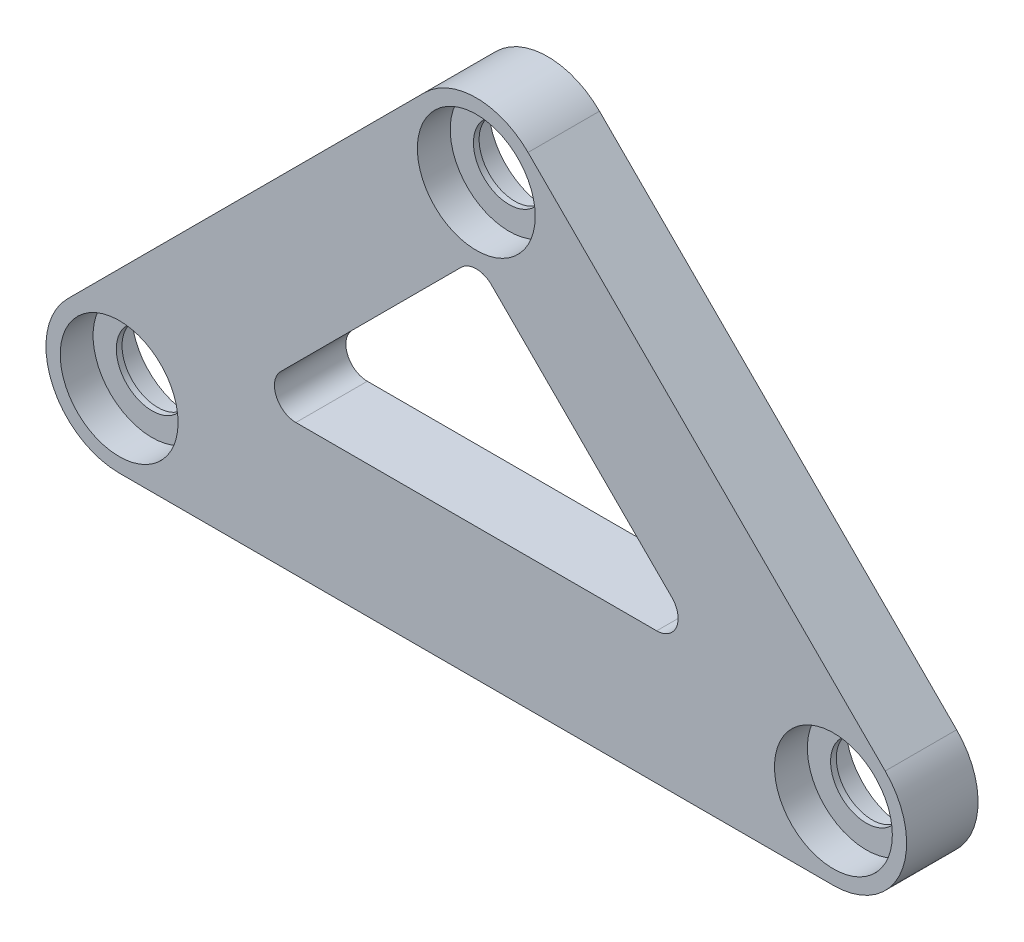
SolidWorks part; units mm, degrees
ref_plane "Front Plane" through (0, 0, 0) normal (0, 0, 1) x (1, 0, 0)
ref_plane "Top Plane" through (0, 0, 0) normal (0, 1, 0) x (1, 0, 0)
ref_plane "Right Plane" through (0, 0, 0) normal (1, 0, 0) x (0, 0, -1)
sketch "Sketch2" plane through (0, 0, 0) normal (0, 0, 1) x (1, 0, 0)
  line L0 (-100, 0) -> (0, 0) construction
  line L1 (-100, 10.25) -> (0, 10.25)
  line L2 (-100, -10.25) -> (0, -10.25)
  line L3 (0, 0) -> (-50, 50) construction
  line L4 (-7.2478, -7.2478) -> (-57.2478, 42.7522)
  line L5 (7.2478, 7.2478) -> (-42.7522, 57.2478)
  line L6 (-100, 0) -> (-50, 50) construction
  line L7 (-107.2478, 7.2478) -> (-57.2478, 57.2478)
  line L8 (-92.7522, -7.2478) -> (-42.7522, 42.7522)
  arc A0 (-100, 10.25) -> (-100, -10.25) centre (-100, 0) ccw
  arc A1 (0, -10.25) -> (0, 10.25) centre (0, 0) ccw
  arc A2 (-7.2478, -7.2478) -> (7.2478, 7.2478) centre (0, 0) ccw
  arc A3 (-42.7522, 57.2478) -> (-57.2478, 42.7522) centre (-50, 50) ccw
  arc A4 (-107.2478, 7.2478) -> (-92.7522, -7.2478) centre (-100, 0) ccw
  arc A5 (-42.7522, 42.7522) -> (-57.2478, 57.2478) centre (-50, 50) ccw
  point P3 (-50, 0)
  point P8 (-25, 25)
  point P15 (-75, 25)
  point P22 (-19.863, 86.6025)
  point P23 (-22.8801, 46.2137)
  point P24 (-75.429, 10.25)
  point P25 (0, 0)
  dimension "D1" = 100
  dimension "D2" = 20.5
  dimension "D3" = 45
  dimension "D4" = 45
extrude "Boss-Extrude4" add sketch "Sketch2" along normal blind 10 contours A4 L2 A2 L4 L1 L8 | A0 A4 L8 L1 | A3 L7 A0 L1 L8 L4 | L8 A5 A3 L4 | A5 L8 L4 L1 A1 L5 | L4 A2 A1 L1 region at (-74.0722, 27.272, 0) region at (-96.1173, 1.6083, 0) region at (-50, -1.0132, 0) region at (-25.9278, 27.272, 0) region at (-3.8827, 1.6083, 0) region at (-50, 49.2802, 0)
sketch "Sketch3" plane through (0, 0, 0) normal (0, 0, -1) x (-1, 0, 0)
  line L0 (57.2478, 57.2478) -> (107.2478, 7.2478)
  line L1 (57.2478, 57.2478) -> (107.2478, 7.2478)
  line L2 (100, -10.25) -> (0, -10.25)
  line L3 (100, -10.25) -> (0, -10.25)
  line L4 (-7.2478, 7.2478) -> (42.7522, 57.2478)
  line L5 (-7.2478, 7.2478) -> (42.7522, 57.2478)
  circle A0 centre (0, 0) radius 8.25
  circle A1 centre (50, 50) radius 8.25
  circle A2 centre (100, 0) radius 8.25
  arc A3 (100, -10.25) -> (107.2478, 7.2478) centre (100, 0) ccw
  arc A4 (100, -10.25) -> (107.2478, 7.2478) centre (100, 0) ccw
  arc A5 (-7.2478, 7.2478) -> (0, -10.25) centre (0, 0) ccw
  arc A6 (-7.2478, 7.2478) -> (0, -10.25) centre (0, 0) ccw
  arc A7 (57.2478, 57.2478) -> (42.7522, 57.2478) centre (50, 50) ccw
  arc A8 (57.2478, 57.2478) -> (42.7522, 57.2478) centre (50, 50) ccw
  point P7 (0, 0)
  dimension "D1" = 16.5
  dimension "D2" = 16.5
  dimension "D3" = 16.5
extrude "Cut-Extrude1" cut sketch "Sketch3" against normal blind 4.6 contours A0 | A1 | A2 region at (0, 0, 0) region at (-50, 50, 0) region at (-100, 0, 0)
sketch "Sketch4" plane through (0, 0, 10) normal (0, 0, 1) x (1, 0, 0)
  circle A0 centre (-100, 0) radius 8.25
  circle A1 centre (-50, 50) radius 8.25
  circle A2 centre (0, 0) radius 8.25
  arc A3 (-107.2478, 7.2478) -> (-100, -10.25) centre (-100, 0) ccw construction
  arc A4 (-42.7522, 57.2478) -> (-57.2478, 57.2478) centre (-50, 50) ccw construction
  arc A5 (0, -10.25) -> (7.2478, 7.2478) centre (0, 0) ccw construction
  dimension "D1" = 16.5
  dimension "D2" = 16.5
  dimension "D3" = 16.5
extrude "Cut-Extrude2" cut sketch "Sketch4" against normal blind 4.6
sketch "Sketch5" plane through (0, 0, 0) normal (0, 0, -1) x (-1, 0, 0)
  line L2 (17.5, 8.25) -> (50, 40.75)
  line L3 (50, 40.75) -> (82.5, 8.25)
  line L4 (82.5, 8.25) -> (17.5, 8.25)
  circle A0 centre (0, 0) radius 8.25 construction
  circle A2 centre (50, 50) radius 8.25 construction
  point P5 (49.7507, 40.2057)
  point P6 (16.5082, 8.25)
  point P7 (0, 0)
  dimension "D3" = 45
  dimension "D1" = 9.25
  dimension "D2" = 45
extrude "Cut-Extrude3" cut sketch "Sketch5" against normal blind 16.6
sketch "Sketch6" plane through (0, 0, 10) normal (0, 0, 1) x (1, 0, 0)
  circle A1 centre (-100, 0) radius 5
  circle A2 centre (-50, 50) radius 5
  circle A3 centre (0, 0) radius 5
  circle A4 centre (-100, 0) radius 8.25 construction
  circle A6 centre (-50, 50) radius 8.25 construction
  circle A7 centre (0, 0) radius 8.25 construction
  dimension "D1" = 10
  dimension "D2" = 10
  dimension "D3" = 10
extrude "Cut-Extrude4" cut sketch "Sketch6" against normal blind 16.6
fillet "Fillet1" radius 3 3 edges at (-82.5, 8.25, 5) (-17.5, 8.25, 5) (-50, 40.75, 5)
equation "\"D4@Sketch2\"=\"D3@Sketch2\""
equation "\"D2@Sketch3\"=\"D1@Sketch3\""
equation "\"D3@Sketch3\"=\"D1@Sketch3\""
equation "\"D2@Sketch4\"=\"D1@Sketch4\""
equation "\"D3@Sketch4\"=\"D1@Sketch4\""
equation "\"D3@Sketch5\"=\"D2@Sketch5\""
equation "\"D2@Sketch6\"=\"D1@Sketch6\""
equation "\"D3@Sketch6\"=\"D2@Sketch6\""
